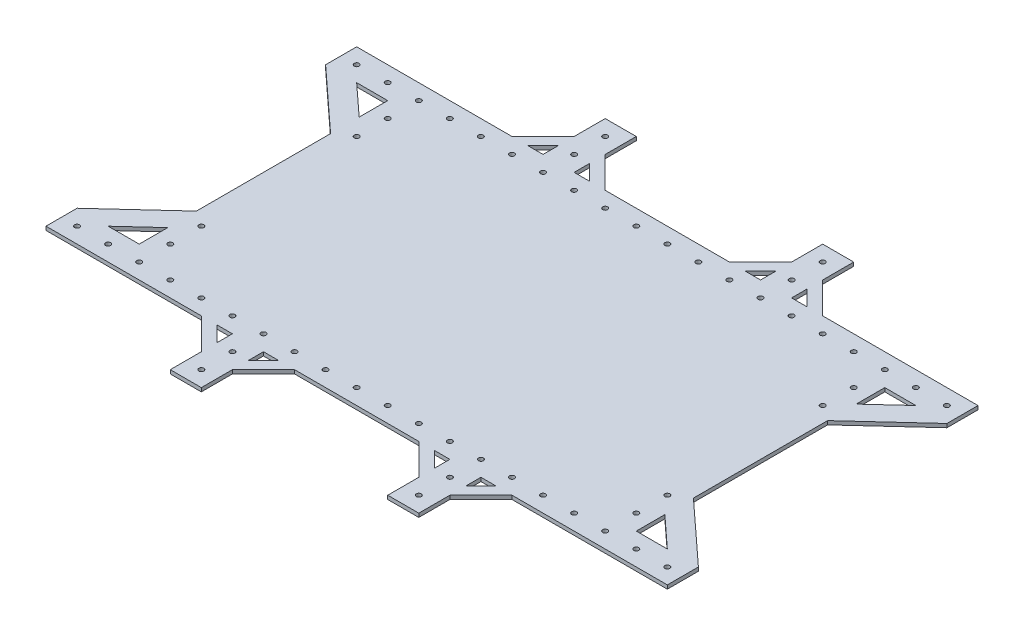
SolidWorks part; units mm, degrees
ref_plane "Front Plane" through (0, 0, 0) normal (0, 0, 1) x (1, 0, 0)
ref_plane "Top Plane" through (0, 0, 0) normal (0, 1, 0) x (1, 0, 0)
ref_plane "Right Plane" through (0, 0, 0) normal (1, 0, 0) x (0, 0, -1)
sketch "Sketch1" plane through (0, 0, 0) normal (0, 1, 0) x (1, 0, 0)
  line L0 (-75, 125) -> (75, 125)
  line L2 (-200, -100) -> (-200, 100)
  line L4 (200, -100) -> (200, 100)
  line L8 (-75, 125) -> (-75, 175)
  line L9 (-75, 175) -> (-100, 175)
  line L10 (-100, 125) -> (-100, 175)
  line L12 (100, 125) -> (100, 175)
  line L13 (100, 175) -> (75, 175)
  line L14 (75, 125) -> (75, 175)
  line L16 (-100, -125) -> (-100, -175)
  line L17 (-100, -175) -> (-75, -175)
  line L18 (-75, -125) -> (-75, -175)
  line L20 (75, -125) -> (75, -175)
  line L21 (75, -175) -> (100, -175)
  line L22 (100, -125) -> (100, -175)
  line L25 (-200, 100) -> (-250, 100)
  line L26 (-250, 125) -> (-250, 100)
  line L29 (200, 100) -> (250, 100)
  line L30 (250, 125) -> (250, 100)
  line L33 (-200, -100) -> (-250, -100)
  line L34 (-250, -125) -> (-250, -100)
  line L37 (200, -100) -> (250, -100)
  line L38 (250, -125) -> (250, -100)
  line L39 (-75, -125) -> (75, -125)
  line L42 (-250, -125) -> (-100, -125)
  line L43 (250, -125) -> (100, -125)
  line L44 (-100, 125) -> (-250, 125)
  line L45 (250, 125) -> (100, 125)
  point P0 (0, 0)
  point P1 (0, -125)
  point P2 (200, 0)
  point P3 (0, 0)
  point P28 (250, 112.5)
  dimension "D1" = 400
  dimension "D3" = 125
  dimension "D4" = 25
  dimension "D5" = 150
  dimension "D6" = 150
  dimension "D7" = 25
  dimension "D8" = 25
  dimension "D9" = 25
  dimension "D10" = 150
  dimension "D11" = 50
  dimension "D12" = 25
  dimension "D13" = 50
  dimension "D14" = 25
  dimension "D15" = 50
  dimension "D16" = 50
  dimension "D17" = 50
  dimension "D18" = 50
  dimension "D19" = 250
  dimension "D20" = 50
  dimension "D21" = 250
  dimension "D22" = 50
  dimension "D23" = 250
  dimension "D24" = 25
  dimension "D25" = 25
  dimension "D26" = 50
extrude "Boss-Extrude1" add sketch "Sketch1" along normal blind 3
sketch "Sketch2" plane through (0, 3, 0) normal (0, 1, 0) x (1, 0, 0)
  line L0 (-100, 150) -> (-125, 125)
  line L1 (-100, 175) -> (-100, 125) construction
  line L2 (-100, 125) -> (-250, 125) construction
  line L3 (-100, 137.5) -> (-112.5, 125)
  line L4 (-100, 150) -> (-100, 137.5)
  line L5 (-125, 125) -> (-112.5, 125)
  line L6 (-75, 150) -> (-50, 125)
  line L7 (-75, 125) -> (-75, 175) construction
  line L8 (75, 125) -> (-75, 125) construction
  line L9 (-75, 137.5) -> (-62.5, 125)
  line L10 (-75, 150) -> (-75, 137.5)
  line L11 (-50, 125) -> (-62.5, 125)
  line L12 (75, 150) -> (50, 125)
  line L13 (75, 175) -> (75, 125) construction
  line L14 (75, 137.5) -> (62.5, 125)
  line L15 (100, 150) -> (125, 125)
  line L16 (100, 125) -> (100, 175) construction
  line L17 (250, 125) -> (100, 125) construction
  line L18 (100, 137.5) -> (112.5, 125)
  line L19 (75, 150) -> (75, 137.5)
  line L20 (50, 125) -> (62.5, 125)
  line L21 (100, 150) -> (100, 137.5)
  line L22 (112.5, 125) -> (125, 125)
  line L23 (-75, -150) -> (-50, -125)
  line L24 (-75, -175) -> (-75, -125) construction
  line L25 (-75, -125) -> (75, -125) construction
  line L26 (-62.5, -125) -> (-75, -137.5)
  line L27 (-100, -150) -> (-125, -125)
  line L28 (-100, -125) -> (-100, -175) construction
  line L29 (-250, -125) -> (-100, -125) construction
  line L30 (-100, -137.5) -> (-112.5, -125)
  line L31 (-112.5, -125) -> (-125, -125)
  line L32 (-100, -150) -> (-100, -137.5)
  line L33 (-75, -137.5) -> (-75, -150)
  line L34 (-62.5, -125) -> (-50, -125)
  line L35 (75, -150) -> (50, -125)
  line L36 (75, -125) -> (75, -175) construction
  line L37 (62.5, -125) -> (75, -137.5)
  line L38 (100, -150) -> (125, -125)
  line L39 (100, -175) -> (100, -125) construction
  line L40 (100, -125) -> (250, -125) construction
  line L41 (100, -137.5) -> (112.5, -125)
  line L42 (62.5, -125) -> (50, -125)
  line L43 (75, -137.5) -> (75, -150)
  line L44 (100, -137.5) -> (100, -150)
  line L45 (112.5, -125) -> (125, -125)
  dimension "D1" = 25
  dimension "D2" = 12.5
  dimension "D3" = 12.5
  dimension "D4" = 25
  dimension "D5" = 12.5
  dimension "D6" = 12.5
  dimension "D7" = 25
  dimension "D8" = 12.5
  dimension "D9" = 12.5
  dimension "D10" = 25
  dimension "D11" = 12.5
  dimension "D12" = 12.5
  dimension "D13" = 25
  dimension "D14" = 12.5
  dimension "D15" = 12.5
  dimension "D16" = 25
  dimension "D17" = 12.5
  dimension "D18" = 12.5
  dimension "D19" = 12.5
  dimension "D20" = 12.5
  dimension "D21" = 25
  dimension "D22" = 25
  dimension "D23" = 12.5
  dimension "D24" = 12.5
extrude "Boss-Extrude2" add sketch "Sketch2" against normal blind 3
sketch "Sketch3" plane through (0, 3, 0) normal (0, 1, 0) x (1, 0, 0)
  line L0 (-250, 100) -> (-200, 54)
  line L1 (-200, 100) -> (-200, -100) construction
  line L2 (-250, 100) -> (-200, 100) construction
  line L3 (-225, 100) -> (-200, 77)
  line L4 (250, 100) -> (200, 54)
  line L5 (200, -100) -> (200, 100) construction
  line L6 (225, 100) -> (200, 77)
  line L7 (200, 100) -> (250, 100) construction
  line L8 (-250, -100) -> (-200, -54)
  line L9 (-225, -100) -> (-200, -77)
  line L10 (-200, -100) -> (-250, -100) construction
  line L11 (250, -100) -> (200, -54)
  line L12 (225, -100) -> (200, -77)
  line L13 (250, -100) -> (200, -100) construction
  line L14 (-250, 100) -> (-225, 100)
  line L15 (-200, 77) -> (-200, 54)
  line L16 (200, 77) -> (200, 54)
  line L17 (250, 100) -> (225, 100)
  line L18 (225, -100) -> (250, -100)
  line L19 (200, -54) -> (200, -77)
  line L20 (-250, -100) -> (-225, -100)
  line L21 (-200, -54) -> (-200, -77)
  dimension "D1" = 46
  dimension "D2" = 23
  dimension "D3" = 46
  dimension "D4" = 23
  dimension "D5" = 46
  dimension "D6" = 23
  dimension "D7" = 46
  dimension "D8" = 23
extrude "Boss-Extrude3" add sketch "Sketch3" against normal blind 3
sketch "Sketch4" plane through (0, 3, 0) normal (0, 1, 0) x (1, 0, 0)
  line L0 (-250, 125) -> (-250, 100) construction
  line L1 (-125, 125) -> (-250, 125) construction
  line L2 (-250, -100) -> (-250, -125) construction
  line L3 (-250, -125) -> (-125, -125) construction
  circle A0 centre (-237.5, 112.5) radius 2
  circle A1 centre (-212.5, 112.5) radius 2
  circle A2 centre (-187.5, 112.5) radius 2
  circle A3 centre (-162.5, 112.5) radius 2
  circle A4 centre (-137.5, 112.5) radius 2
  circle A5 centre (-112.5, 112.5) radius 2
  circle A6 centre (-87.5, 112.5) radius 2
  circle A7 centre (-62.5, 112.5) radius 2
  circle A8 centre (-37.5, 112.5) radius 2
  circle A9 centre (-12.5, 112.5) radius 2
  circle A10 centre (12.5, 112.5) radius 2
  circle A11 centre (37.5, 112.5) radius 2
  circle A12 centre (62.5, 112.5) radius 2
  circle A13 centre (87.5, 112.5) radius 2
  circle A14 centre (112.5, 112.5) radius 2
  circle A15 centre (137.5, 112.5) radius 2
  circle A16 centre (162.5, 112.5) radius 2
  circle A17 centre (187.5, 112.5) radius 2
  circle A18 centre (212.5, 112.5) radius 2
  circle A19 centre (237.5, 112.5) radius 2
  circle A20 centre (-237.5, -112.5) radius 2
  circle A21 centre (-212.5, -112.5) radius 2
  circle A22 centre (-187.5, -112.5) radius 2
  circle A23 centre (-162.5, -112.5) radius 2
  circle A24 centre (-137.5, -112.5) radius 2
  circle A25 centre (-112.5, -112.5) radius 2
  circle A26 centre (-87.5, -112.5) radius 2
  circle A27 centre (-62.5, -112.5) radius 2
  circle A28 centre (-37.5, -112.5) radius 2
  circle A29 centre (-12.5, -112.5) radius 2
  circle A30 centre (12.5, -112.5) radius 2
  circle A31 centre (37.5, -112.5) radius 2
  circle A32 centre (62.5, -112.5) radius 2
  circle A33 centre (87.5, -112.5) radius 2
  circle A34 centre (112.5, -112.5) radius 2
  circle A35 centre (137.5, -112.5) radius 2
  circle A36 centre (162.5, -112.5) radius 2
  circle A37 centre (187.5, -112.5) radius 2
  circle A38 centre (212.5, -112.5) radius 2
  circle A39 centre (237.5, -112.5) radius 2
  circle A40 centre (-187.5, 87.5) radius 2
  circle A41 centre (-187.5, 62.5) radius 2
  circle A42 centre (-87.5, 137.5) radius 2
  circle A43 centre (-87.5, 162.5) radius 2
  circle A44 centre (87.5, 137.5) radius 2
  circle A45 centre (87.5, 162.5) radius 2
  circle A46 centre (187.5, 87.5) radius 2
  circle A47 centre (187.5, 62.5) radius 2
  circle A48 centre (-187.5, -87.5) radius 2
  circle A49 centre (-187.5, -62.5) radius 2
  circle A50 centre (-87.5, -137.5) radius 2
  circle A51 centre (-87.5, -162.5) radius 2
  circle A52 centre (87.5, -137.5) radius 2
  circle A53 centre (87.5, -162.5) radius 2
  circle A54 centre (187.5, -87.5) radius 2
  circle A55 centre (187.5, -62.5) radius 2
  dimension "D1" = 4
  dimension "D6" = 4
  dimension "D2" = 12.5
  dimension "D3" = 12.5
  dimension "D5" = 25
  dimension "D7" = 12.5
  dimension "D8" = 12.5
  dimension "D10" = 25
  dimension "D12" = 25
  dimension "D14" = 25
  dimension "D16" = 25
  dimension "D18" = 25
  dimension "D20" = 25
  dimension "D22" = 25
  dimension "D24" = 25
  dimension "D26" = 25
  dimension "D4" = 20
  dimension "D9" = 20
  dimension "D11" = 3
  dimension "D13" = 3
  dimension "D15" = 3
  dimension "D17" = 3
  dimension "D19" = 3
  dimension "D21" = 3
  dimension "D23" = 3
  dimension "D25" = 3
extrude "Cut-Extrude1" cut sketch "Sketch4" against normal blind 3
